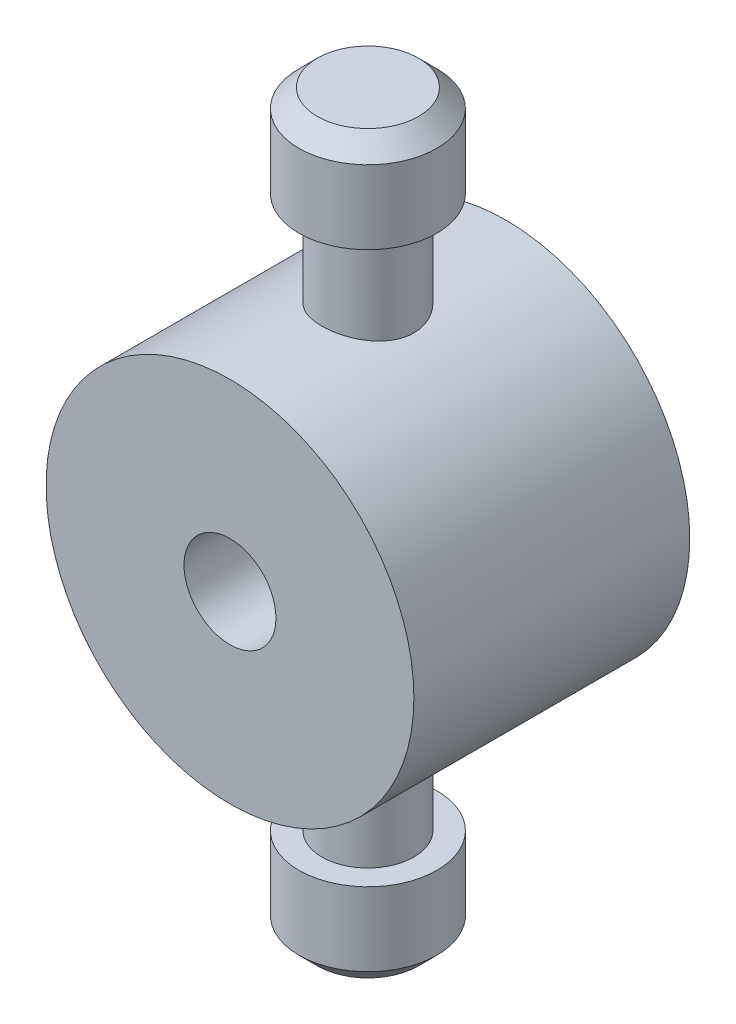
SolidWorks part; units mm, degrees
ref_plane "Front Plane" through (0, 0, 0) normal (0, 0, 1) x (1, 0, 0)
ref_plane "Top Plane" through (0, 0, 0) normal (0, 1, 0) x (1, 0, 0)
ref_plane "Right Plane" through (0, 0, 0) normal (1, 0, 0) x (0, 0, -1)
sketch "Sketch1" plane through (0, 0, 0) normal (0, 0, 1) x (1, 0, 0)
  circle A0 centre (0, 0) radius 20
  dimension "D1" = 40
extrude "Boss-Extrude1" add sketch "Sketch1" along normal blind 30
sketch "Sketch2" plane through (0, 0, 0) normal (0, 1, 0) x (1, 0, 0)
  line L0 (0, 0) -> (0, -15) construction
  circle A0 centre (0, -15) radius 5
  dimension "D2" = 10
  dimension "D1" = 15
extrude "Boss-Extrude2" add sketch "Sketch2" along normal blind 30 and the other way blind 30
sketch "Sketch3" plane through (0, 30, 0) normal (0, 1, 0) x (1, 0, 0)
  circle A0 centre (0, -15) radius 7.5
  dimension "D1" = 15
extrude "Boss-Extrude3" add sketch "Sketch3" along normal blind 10
chamfer "Chamfer1" distance 2 angle 45 1 edges at (0, 40, 22.5)
mirror "Mirror1" about plane through (0, 0, 0) normal (0, 1, 0) of "Chamfer1", "Boss-Extrude3"
sketch "Sketch4" plane through (0, 0, 30) normal (0, 0, 1) x (1, 0, 0)
  circle A0 centre (0, 0) radius 5
  dimension "D1" = 10
extrude "Cut-Extrude1" cut sketch "Sketch4" against normal blind 10
